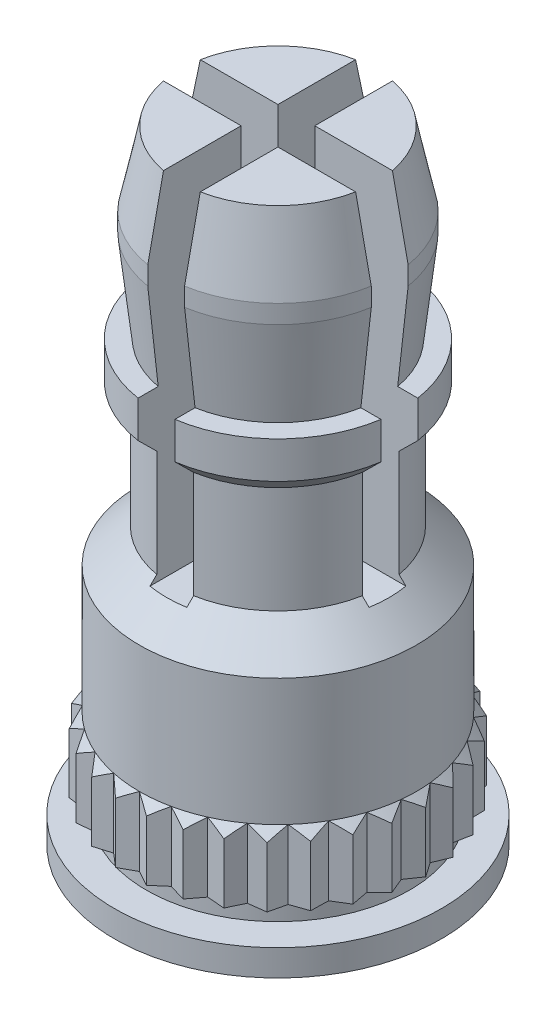
SolidWorks part; units mm, degrees
revolve "Body" add sketch "BodySke" angle 360 about L9 other way angle 12
sketch "BodySke" plane through (0, 0, 0) normal (0, 0, 1) x (1, 0, 0)
  line L0 (2.5555, 0) -> (2.5555, 0.3825)
  line L1 (2.69, 4.1891) -> (2.0272, 4.8518)
  line L2 (2.87, 1.5475) -> (2.69, 1.7275)
  line L3 (2.0272, 4.8518) -> (2.0272, 6.9267)
  line L4 (0, -0.51) -> (3.175, -0.51)
  line L5 (3.175, -0.51) -> (3.175, 0)
  line L6 (3.175, 0) -> (2.5555, 0)
  line L7 (2.385, 7.2845) -> (2.385, 8)
  line L8 (2.69, 1.7275) -> (2.69, 4.1891)
  line L9 (0, -0.51) -> (0, 17.145) construction
  line L10 (2.385, 8) -> (2, 8)
  line L11 (2, 8) -> (2.2, 9.79)
  line L12 (2.2, 9.79) -> (2.2, 10.148)
  line L13 (2.2, 10.148) -> (1.9, 11.58)
  line L14 (1.9, 11.58) -> (0, 11.58)
  line L15 (2.5555, 0.3825) -> (2.87, 0.3825)
  line L16 (2.87, 0.3825) -> (2.87, 1.5475)
  line L17 (0, 11.58) -> (0, -0.51)
  line L19 (2.385, 7.2845) -> (2.0272, 6.9267)
  dimension "Clinch_dia" = 5.74
  dimension "T_ht" = 0.51
  dimension "D4" = 45
ref_plane "Plane1" through (0, 0, 0) normal (0, 0, 1) x (1, 0, 0)
ref_plane "Plane2" through (0, 0, 0) normal (0, 1, 0) x (1, 0, 0)
ref_plane "Plane3" through (0, 0, 0) normal (1, 0, 0) x (0, 0, -1)
sketch "SlitCutSke" plane through (0, 11.58, 0) normal (0, 1, 0) x (-1, 0, 0)
  line L0 (-2.6661, 0.3578) -> (2.6661, 0.3578)
  line L1 (2.6661, -0.3578) -> (-2.6661, -0.3578)
  line L2 (-2.6661, 0.3578) -> (-2.6661, -0.3578)
  line L3 (2.6661, 0.3578) -> (2.6661, -0.3578)
  line L4 (-4.064, 0) -> (4.064, 0) construction
  circle A1 centre (0, 0) radius 2.69 construction
extrude "SlitCut" cut sketch "SlitCutSke" against normal blind 6.8582
pattern_circular "SlitCutPat" count 2 every 90 about axis through (0, -0.51, 0) along (0, 1, 0) of "SlitCut"
ref_plane "Plane4" through (0, -0.5486, 0) normal (0, 1, 0) x (-1, 0, 0)
sketch "CliRinCutSke" plane through (0, 0.3825, 0) normal (0, -1, 0) x (1, 0, 0)
  line L0 (0.3, 2.8543) -> (0, 2.69)
  line L1 (0, 2.69) -> (-0.3, 2.8543)
  line L2 (0, 0) -> (0, 5.842) construction
  arc A1 (0.3, 2.8543) -> (-0.3, 2.8543) centre (0, 0) ccw
  circle A2 centre (0, 0) radius 2.69 construction
  dimension "Clinch_dia" = 5.74
  dimension "Angle" = 12
extrude "ClinchCut" cut sketch "CliRinCutSke" against normal blind 1.345
pattern_circular "ClinchCutPat" count 30 every 12 about axis through (0, -0.51, 0) along (0, 1, 0) of "ClinchCut"
equation "' \"Panel_dia@BodySke\" = 4"
equation "' \"Length@BodySke\" = 8"
equation "' \"B_dia@BodySke\" = 4.77"
equation "' \"C_dia@BodySke\" = 5.38"
equation "' \"D_ht@BodySke\" = 3.58"
equation "' \"H_dia@BodySke\" = 6.35"
equation "' \"T_ht@BodySke\" = 0.51"
equation "' \"Clinch_dia@BodySke\" = 5.74"
equation "\"Tip_dia@BodySke\" = \"Panel_dia@BodySke\" * 0.95"
equation "\"Slip_dia@BodySke\" = \"Panel_dia@BodySke\" * 1.1"
equation "\"Slip_ht@BodySke\" = \"D_ht@BodySke\" * 0.1"
equation "\"Grip_ht@BodySke\" = \"D_ht@BodySke\" * 0.5"
equation "\"B_ht@BodySke\" = \"B_dia@BodySke\" * 0.15"
equation "\"Neck_dia@BodySke\" = \"B_dia@BodySke\" * 0.85"
equation "\"Neck_len@BodySke\" = \"B_dia@BodySke\" * 0.66"
equation "\"Groove_dia@BodySke\" = \"C_dia@BodySke\" * 0.95"
equation "\"Groove_wid@BodySke\" = \"T_ht@BodySke\" * 0.75"
equation "\"Width@SlitCutSke\" = \"B_ht@BodySke\""
equation "\"Depth@SlitCut\" = \"D_ht@BodySke\" + \"Neck_len@BodySke\" + 0.13"
equation "\"Clinch_lim@BodySke\" = \"C_dia@BodySke\" * 0.25"
equation "\"Count@ClinchCutPat\" = 30"
equation "\"Angle@ClinchCutPat\" = 360 / \"Count@ClinchCutPat\""
equation "\"Angle@CliRinCutSke\" = 360 / \"Count@ClinchCutPat\""
equation "\"Clinch_dia@CliRinCutSke\" = \"Clinch_dia@BodySke\""
equation "\"Clinch_minor@CliRinCutSke\" = \"C_dia@BodySke\""
equation "\"Depth@ClinchCut\" = \"Clinch_lim@BodySke\""
